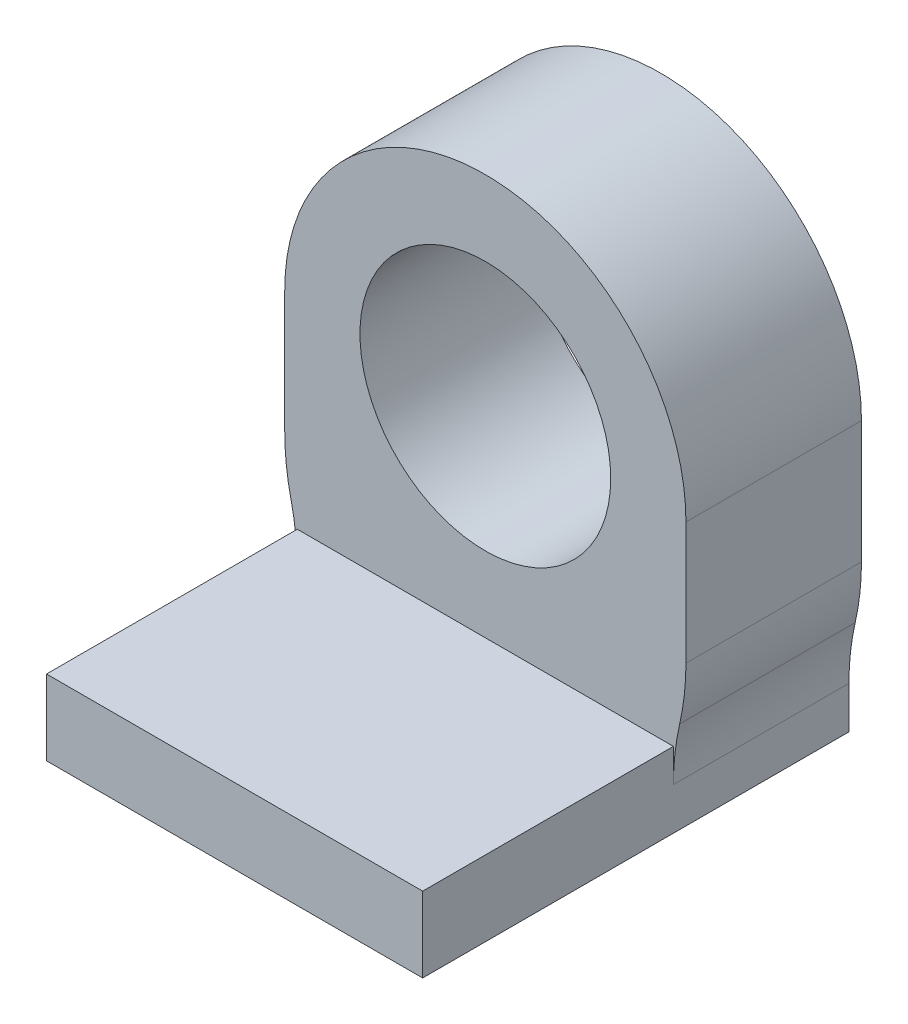
SolidWorks part; units mm, degrees
ref_plane "Front Plane" through (0, 0, 0) normal (0, 0, 1) x (1, 0, 0)
ref_plane "Top Plane" through (0, 0, 0) normal (0, 1, 0) x (1, 0, 0)
ref_plane "Right Plane" through (0, 0, 0) normal (1, 0, 0) x (0, 0, -1)
sketch "Sketch1" plane through (0, 0, 0) normal (0, 0, 1) x (1, 0, 0)
  line L0 (-8, 0) -> (-8, -8)
  line L1 (-8, -8) -> (-7.5, -8)
  line L2 (-7.5, -8) -> (-7.5, -11)
  line L3 (-7.5, -11) -> (7.5, -11)
  line L4 (7.5, -11) -> (7.5, -8)
  line L5 (7.5, -8) -> (8, -8)
  line L6 (8, -8) -> (8, 0)
  line L7 (0, 0) -> (0, -11) construction
  circle A0 centre (0, 0) radius 5
  arc A1 (8, 0) -> (-8, 0) centre (0, 0) ccw
  dimension "D1" = 10
  dimension "D2" = 3
  dimension "D3" = 3
  dimension "D4" = 15
extrude "Boss-Extrude1" add sketch "Sketch1" along normal blind 7
sketch "Sketch2" plane through (0, 0, 7) normal (0, 0, 1) x (1, 0, 0)
  line L1 (-7.5, -11) -> (7.5, -11)
  line L2 (-7.5, -11) -> (-7.5, -8)
  line L3 (-7.5, -8) -> (7.5, -8)
  line L4 (7.5, -11) -> (7.5, -8)
extrude "Boss-Extrude2" add sketch "Sketch2" along normal blind 10
fillet "Fillet1" radius 10 2 edges at (-8, -8, 3.5) (8, -8, 3.5)
fillet "Fillet2" radius 10 2 edges at (7.5, -8, 3.5) (-7.5, -8, 3.5)
